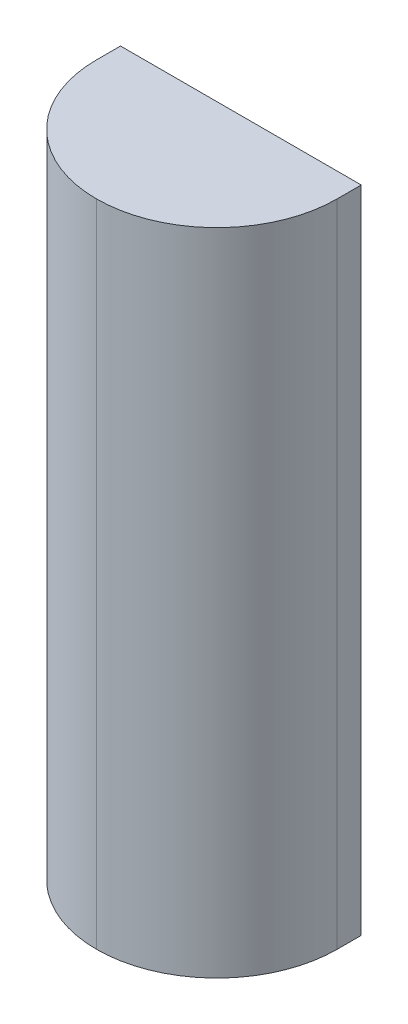
SolidWorks part; units mm, degrees
ref_plane "Alzado" through (0, 0, 0) normal (0, 0, 1) x (1, 0, 0)
ref_plane "Planta" through (0, 0, 0) normal (0, 1, 0) x (1, 0, 0)
ref_plane "Vista lateral" through (0, 0, 0) normal (1, 0, 0) x (0, 0, -1)
sketch "Croquis1" plane through (0, 0, 0) normal (0, 0, 1) x (1, 0, 0)
  line L0 (6.35, 0) -> (1.85, 0) construction
  line L1 (6.35, -2.9) -> (6.35, 2.9) construction
  line L3 (1.35, 1.35) -> (2.35, 1.35)
  line L4 (1.35, 1.35) -> (1.35, -1.35)
  line L5 (1.35, -1.35) -> (2.35, -1.35)
  line L6 (2.35, 1.35) -> (2.35, -1.35)
  line L7 (1.35, 1.35) -> (2.35, -1.35) construction
  line L8 (1.35, -1.35) -> (2.35, 1.35) construction
  dimension "D1" = 4.5
  dimension "D2" = 1
  dimension "D3" = 2.7
extrude "Saliente-Extruir1" add sketch "Croquis1" along normal blind 0.6
fillet "Redondeo1" radius 0.5 2 edges at (2.35, 0, 0.6) (1.35, 0, 0.6)
